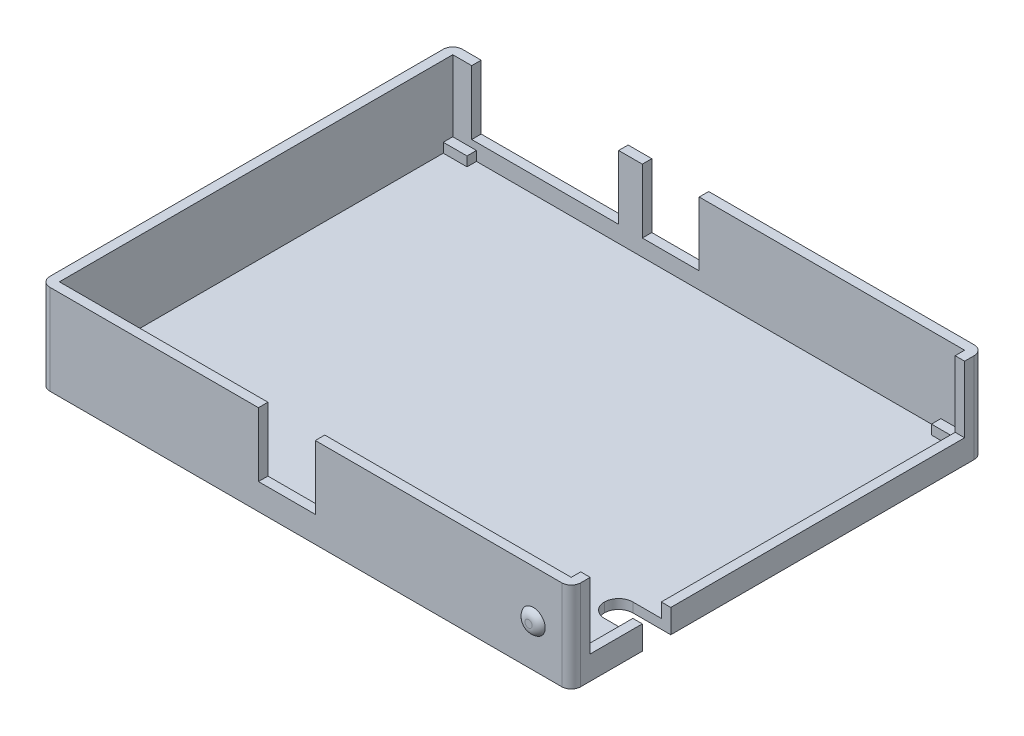
SolidWorks part; units mm, degrees
material "Plain Carbon Steel"
ref_plane "Front Plane" through (0, 0, 0) normal (0, 0, 1) x (1, 0, 0)
ref_plane "Top Plane" through (0, 0, 0) normal (0, 1, 0) x (1, 0, 0)
ref_plane "Right Plane" through (0, 0, 0) normal (1, 0, 0) x (0, 0, -1)
sketch "Sketch1" plane through (0, 0, 0) normal (0, 1, 0) x (1, 0, 0)
  line L1 (0, 0) -> (-112, 0)
  line L2 (0, 0) -> (0, 87)
  line L3 (0, 87) -> (-112, 87)
  line L4 (-112, 0) -> (-112, 87)
  dimension "D1" = 112
  dimension "D2" = 87
extrude "Boss-Extrude1" add sketch "Sketch1" along normal blind 19
sketch "Sketch3" plane through (0, 19, 0) normal (0, 1, 0) x (1, 0, 0)
  line L0 (-112, 87) -> (-112, 0) construction
  line L1 (-110, 85) -> (-2, 85)
  line L2 (-110, 85) -> (-110, 2)
  line L3 (-110, 2) -> (-2, 2)
  line L4 (-2, 85) -> (-2, 2)
  line L5 (0, 87) -> (-112, 87) construction
  line L6 (-112, 0) -> (0, 0) construction
  dimension "D1" = 108
  dimension "D2" = 2
  dimension "D3" = 2
  dimension "D4" = 2
extrude "Cut-Extrude1" cut sketch "Sketch3" against normal blind 17
sketch "Sketch4" plane through (0, 2, 0) normal (0, 1, 0) x (1, 0, 0)
  line L0 (-2, 85) -> (-110, 85) construction
  line L1 (-110, 85) -> (-105, 85)
  line L2 (-110, 85) -> (-110, 83)
  line L3 (-110, 83) -> (-105, 83)
  line L4 (-105, 85) -> (-105, 83)
  line L5 (-110, 85) -> (-110, 2) construction
  dimension "D1" = 0
  dimension "D2" = 0
  dimension "D3" = 5
  dimension "D4" = 2
extrude "Boss-Extrude3" add sketch "Sketch4" along normal blind 2
sketch "Sketch5" plane through (0, 2, 0) normal (0, 1, 0) x (1, 0, 0)
  line L0 (-2, 85) -> (-110, 85) construction
  line L1 (-7, 85) -> (-2, 85)
  line L2 (-7, 85) -> (-7, 83)
  line L3 (-7, 83) -> (-2, 83)
  line L4 (-2, 85) -> (-2, 83)
  line L5 (-2, 2) -> (-2, 85) construction
  dimension "D1" = 5
  dimension "D2" = 2
  dimension "D3" = 0
  dimension "D4" = 0
extrude "Boss-Extrude4" add sketch "Sketch5" along normal blind 2
sketch "Sketch6" plane through (0, 2, 0) normal (0, 1, 0) x (1, 0, 0)
  line L1 (-110, 2) -> (-105, 2)
  line L2 (-110, 2) -> (-110, 4)
  line L3 (-110, 4) -> (-105, 4)
  line L4 (-105, 2) -> (-105, 4)
  dimension "D1" = 5
  dimension "D2" = 2
  dimension "D3" = 0
extrude "Boss-Extrude5" add sketch "Sketch6" along normal blind 2
sketch "Sketch7" plane through (0, 2, 0) normal (0, 1, 0) x (1, 0, 0)
  line L1 (-2, 2) -> (-7, 2)
  line L2 (-2, 2) -> (-2, 4)
  line L3 (-2, 4) -> (-7, 4)
  line L4 (-7, 2) -> (-7, 4)
  dimension "D1" = 5
  dimension "D2" = 2
  dimension "D3" = 0
extrude "Boss-Extrude6" add sketch "Sketch7" along normal blind 2
sketch "Sketch8" plane through (0, 0, 0) normal (0, 0, 1) x (1, 0, 0)
  line L0 (-112, 19) -> (-112, 0) construction
  line L1 (-66, 19) -> (-54, 19)
  line L2 (-66, 19) -> (-66, 5.5)
  line L3 (-66, 5.5) -> (-54, 5.5)
  line L4 (-54, 19) -> (-54, 5.5)
  line L5 (-112, 0) -> (0, 0) construction
  line L8 (-112, 19) -> (0, 19) construction
  dimension "D1" = 46
  dimension "D2" = 12
  dimension "D3" = 5.5
  dimension "D4" = 0
extrude "Cut-Extrude2" cut sketch "Sketch8" against normal blind 2
sketch "Sketch9" plane through (0, 0, -87) normal (0, 0, -1) x (-1, 0, 0)
  line L0 (112, 19) -> (112, 0) construction
  line L1 (106, 19) -> (75, 19)
  line L2 (106, 19) -> (106, 5.5)
  line L3 (106, 5.5) -> (75, 5.5)
  line L4 (75, 19) -> (75, 5.5)
  line L5 (0, 0) -> (112, 0) construction
  line L6 (0, 19) -> (112, 19) construction
  dimension "D1" = 6
  dimension "D2" = 5.5
  dimension "D3" = 0
  dimension "D4" = 31
extrude "Cut-Extrude3" cut sketch "Sketch9" against normal blind 2
sketch "Sketch10" plane through (0, 0, -87) normal (0, 0, -1) x (-1, 0, 0)
  line L0 (75, 19) -> (75, 5.5) construction
  line L1 (70, 19) -> (58, 19)
  line L2 (70, 19) -> (70, 5.5)
  line L3 (70, 5.5) -> (58, 5.5)
  line L4 (58, 19) -> (58, 5.5)
  line L5 (0, 0) -> (112, 0) construction
  line L6 (0, 19) -> (75, 19) construction
  dimension "D1" = 5
  dimension "D2" = 12
  dimension "D3" = 5.5
  dimension "D4" = 0
extrude "Cut-Extrude4" cut sketch "Sketch10" against normal blind 2
fillet "Fillet2" radius 2 1 edges at (-112, 9.5, 0)
fillet "Fillet3" radius 2 1 edges at (0, 9.5, 0)
fillet "Fillet4" radius 2 1 edges at (0, 9.5, -87)
fillet "Fillet5" radius 2 1 edges at (-112, 9.5, -87)
sketch "Sketch11" plane through (0, 2, 0) normal (0, 1, 0) x (1, 0, 0)
  text T0 "MicroBox"
extrude "Cut-Extrude5" cut sketch "Sketch11" against normal blind 0.5
sketch "Sketch13" plane through (0, 0, 0) normal (1, 0, 0) x (0, 0, -1)
  line L0 (2, 19) -> (2, 0) construction
  line L1 (4, 19) -> (83, 19)
  line L2 (4, 19) -> (4, 5)
  line L3 (4, 5) -> (83, 5)
  line L4 (83, 19) -> (83, 5)
  line L5 (85, 0) -> (85, 19) construction
  line L6 (2, 19) -> (85, 19) construction
  line L7 (2, 0) -> (85, 0) construction
  dimension "D1" = 2
  dimension "D2" = 2
  dimension "D3" = 0
  dimension "D4" = 5
extrude "Cut-Extrude6" cut sketch "Sketch13" against normal blind 2
sketch "Sketch14" plane through (0, 0, 0) normal (1, 0, 0) x (0, 0, -1)
  line L0 (4, 5) -> (83, 5) construction
  line L1 (15, 5) -> (21, 5)
  line L2 (15, 5) -> (15, 0)
  line L3 (15, 0) -> (21, 0)
  line L4 (21, 5) -> (21, 0)
  line L5 (2, 0) -> (85, 0) construction
  line L6 (2, 19) -> (2, 0) construction
  dimension "D1" = 13
  dimension "D2" = 19
extrude "Cut-Extrude8" cut sketch "Sketch14" against normal blind 11
fillet "Fillet6" radius 3 2 edges at (-11, 1, -21) (-11, 1, -15)
sketch "Sketch15" plane through (0, 0, 0) normal (0, 0, 1) x (1, 0, 0)
  line L0 (-2, 0) -> (-2, 19) construction
  line L1 (-54, 19) -> (-2, 19) construction
  circle A1 centre (-8, 9) radius 2.5
  dimension "D2" = 5
  dimension "D1" = 6
  dimension "D3" = 10
extrude "Boss-Extrude7" add sketch "Sketch15" along normal blind 1
sketch "Sketch16" plane through (0, 0, -87) normal (0, 0, -1) x (-1, 0, 0)
  line L0 (2, 19) -> (58, 19) construction
  line L1 (2, 19) -> (2, 0) construction
  circle A0 centre (8, 9) radius 2.5
  point P4 (2, 9.5)
  dimension "D3" = 5
  dimension "D1" = 10
  dimension "D2" = 6
extrude "Boss-Extrude8" add sketch "Sketch16" along normal blind 1
fillet "Fillet8" radius 2 1 edges at (-5.5, 9, 1)
fillet "Fillet9" radius 2 1 edges at (-10.5, 9, -88)
